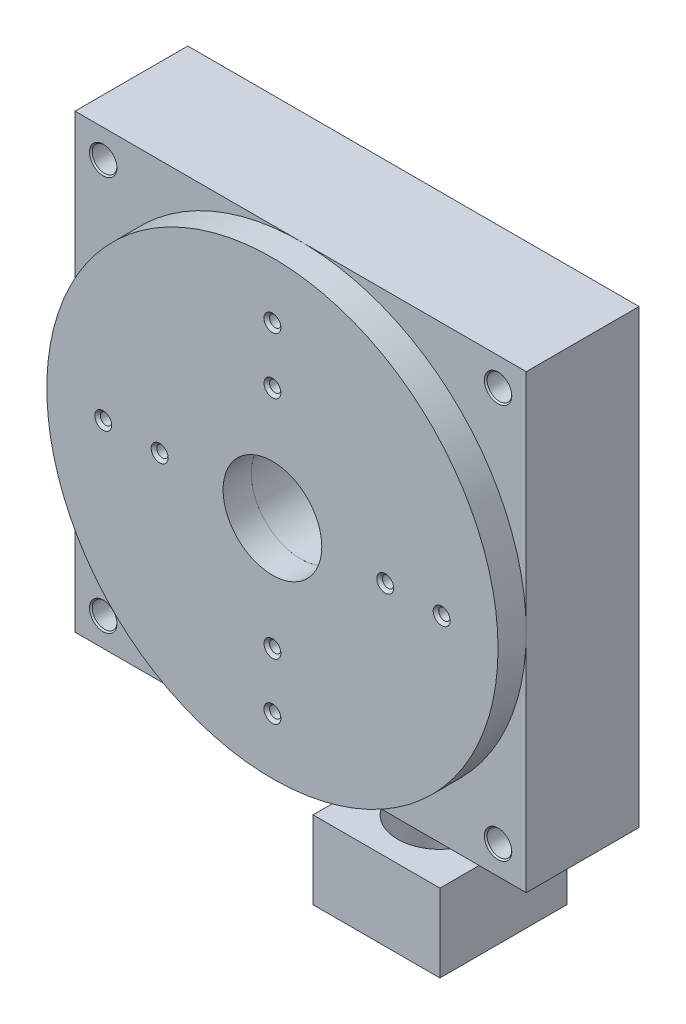
SolidWorks part; units mm, degrees
material "6061-T6 (SS)"
ref_plane "Front Plane" through (0, 0, 0) normal (0, 0, 1) x (1, 0, 0)
ref_plane "Top Plane" through (0, 0, 0) normal (0, 1, 0) x (1, 0, 0)
ref_plane "Right Plane" through (0, 0, 0) normal (1, 0, 0) x (0, 0, -1)
sketch "Sketch1" plane through (0, 0, 0) normal (0, 0, 1) x (1, 0, 0)
  circle A0 centre (0, 0) radius 101.6
  circle A1 centre (0, 0) radius 22.225
  dimension "D1" = 203.2
  dimension "D2" = 44.45
extrude "Boss-Extrude1" add sketch "Sketch1" along normal blind 12.7
hole_wizard "1/4-20 Tapped Hole1" positions "Sketch2" profile "Sketch3" tap size "1/4-20" standard "ANSI Inch" end condition up to next
sketch "Sketch2" plane through (0, 0, 12.7) normal (0, 0, 1) x (1, 0, 0)
  line L0 (0, 0) -> (0, 76.2) construction
  point P2 (0, 76.2)
  point P8 (0, 50.8)
  point P13 (76.2, 0)
  point P14 (50.8, 0)
  point P15 (0, -76.2)
  point P16 (0, -50.8)
  point P17 (-76.2, 0)
  point P18 (-50.8, 0)
  dimension "D1" = 50.8
  dimension "D2" = 76.2
  dimension "D3" = 4
cosmetic thread "Hole Thread1"
cosmetic thread "Hole Thread2"
cosmetic thread "Hole Thread3"
cosmetic thread "Hole Thread4"
cosmetic thread "Hole Thread5"
cosmetic thread "Hole Thread6"
cosmetic thread "Hole Thread7"
cosmetic thread "Hole Thread8"
sketch "Sketch3" plane through (-50.8, 0, 12.7) normal (1, 0, 0) x (0, -1, 0)
  line L0 (0, 0) -> (0, 12.7)
  line L1 (0, 12.7) -> (3.81, 12.7)
  line L2 (2.5527, 11.4427) -> (2.5527, 1.2573)
  line L3 (2.5527, 1.2573) -> (3.81, 0)
  line L5 (3.81, 0) -> (0, 0)
  line L6 (-2.5527, 1.2573) -> (-3.81, 0) construction
  line L7 (3.81, 12.7) -> (2.5527, 11.4427)
  line L8 (-3.81, 12.7) -> (-2.5527, 11.4427) construction
  line L11 (0, -6.35) -> (0, 107.95) construction
  dimension "Thru Tap Drill Dia." = 5.1054
  dimension "Thru Tap Drill Depth" = 12.7
  dimension "Near C'Sink Dia." = 7.62
  dimension "Near C'Sink Angle" = 90
  dimension "Far C'Sink Dia." = 7.62
  dimension "Far C'Sink Angle" = 90
sketch "Sketch4" plane through (0, 0, 0) normal (0, 0, -1) x (-1, 0, 0)
  line L1 (101.6, 101.6) -> (-101.6, 101.6)
  line L2 (101.6, 101.6) -> (101.6, -101.6)
  line L3 (101.6, -101.6) -> (-101.6, -101.6)
  line L4 (-101.6, 101.6) -> (-101.6, -101.6)
  line L5 (0, -101.6) -> (0, 101.6) construction
  line L6 (101.6, 0) -> (-101.6, 0) construction
  circle A1 centre (0, 0) radius 22.225
  circle A2 centre (0, 0) radius 22.225 construction
  point P0 (0, 0)
  dimension "D1" = 203.2
extrude "Boss-Extrude2" add sketch "Sketch4" along normal blind 50.8 separate body
hole_wizard "CBORE for 1/4 Socket Head Cap Screw1" positions "Sketch5" profile "Sketch6" counterbore size "1/4" standard "ANSI Inch" end condition up to next
sketch "Sketch5" plane through (0, 0, 0) normal (0, 0, 1) x (1, 0, 0)
  line L1 (88.9, 88.9) -> (-88.9, 88.9) construction
  line L2 (88.9, 88.9) -> (88.9, -88.9) construction
  line L3 (88.9, -88.9) -> (-88.9, -88.9) construction
  line L4 (-88.9, 88.9) -> (-88.9, -88.9) construction
  line L5 (88.9, 88.9) -> (-88.9, -88.9) construction
  line L6 (88.9, -88.9) -> (-88.9, 88.9) construction
  point P2 (-88.9, -88.9)
  point P53 (88.9, 88.9)
  point P54 (88.9, -88.9)
  point P55 (-88.9, 88.9)
  point P61 (0, 0)
  dimension "D1" = 177.8
sketch "Sketch6" plane through (-88.9, -88.9, 0) normal (1, 0, 0) x (0, -1, 0)
  line L0 (0, 0) -> (0, 50.8)
  line L1 (3.2639, 50.165) -> (3.8989, 50.8)
  line L2 (5.5562, 44.45) -> (3.2639, 44.45)
  line L3 (3.2639, 44.45) -> (3.2639, 50.165)
  line L5 (5.5562, 44.45) -> (5.5562, 0.635)
  line L6 (5.5562, 0.635) -> (6.1913, 0)
  line L7 (6.1913, 0) -> (0, 0)
  line L8 (-5.5562, 0.635) -> (-6.1913, 0) construction
  line L11 (0, -6.35) -> (0, 107.95) construction
  line L12 (3.8989, 50.8) -> (0, 50.8)
  line L13 (-3.2639, 50.165) -> (-3.8989, 50.8) construction
  dimension "Thru Hole Dia." = 6.5278
  dimension "Thru Hole Depth" = 50.8
  dimension "C'Bore Dia." = 11.1125
  dimension "C'Bore Depth" = 44.45
  dimension "Near C'Sink Dia." = 12.3825
  dimension "Near C'Sink Angle" = 90
  dimension "Far C'Sink Dia." = 7.7978
  dimension "Far C'Sink Angle" = 90
sketch "Sketch7" plane through (0, -101.6, 0) normal (0, -1, 0) x (1, 0, 0)
  line L0 (101.6, -50.8) -> (-101.6, -50.8) construction
  line L1 (80.391, 17.653) -> (23.241, 17.653)
  line L2 (80.391, 17.653) -> (80.391, -39.497)
  line L3 (80.391, -39.497) -> (23.241, -39.497)
  line L4 (23.241, 17.653) -> (23.241, -39.497)
  line L5 (80.391, 17.653) -> (23.241, -39.497) construction
  line L6 (80.391, -39.497) -> (23.241, 17.653) construction
  circle A0 centre (51.816, -10.922) radius 19.05
  point P0 (51.816, -10.922)
  dimension "D4" = 38.1
  dimension "D1" = 57.15
  dimension "D2" = 51.816
  dimension "D3" = 39.878
extrude "Boss-Extrude3" add sketch "Sketch7" along normal blind 35.052
hole_wizard "#10-24 Tapped Hole1" positions "Sketch8" profile "Sketch10" tap size "#10-24" standard "ANSI Inch"
sketch "Sketch8" plane through (0, -136.652, 0) normal (0, -1, 0) x (-1, 0, 0)
  line L1 (-75.438, 34.544) -> (-28.194, 34.544) construction
  line L2 (-75.438, 34.544) -> (-75.438, -12.7) construction
  line L3 (-75.438, -12.7) -> (-28.194, -12.7) construction
  line L4 (-28.194, 34.544) -> (-28.194, -12.7) construction
  line L7 (-51.816, 29.972) -> (-51.816, -8.128) construction
  line L9 (-28.194, 34.544) -> (-75.438, -12.7) construction
  arc A3 (-36.2079, 0) -> (-67.4241, 0) centre (-51.816, 10.922) ccw construction
  circle A4 centre (-51.816, 10.922) radius 19.05 construction
  point P1 (-28.194, -12.7)
  point P170 (-75.438, 34.544)
  point P171 (-75.438, -12.7)
  point P172 (-28.194, 34.544)
  point P205 (-51.816, 10.922)
  dimension "D1" = 47.244
sketch "Sketch10" plane through (28.194, -136.652, 12.7) normal (1, 0, 0) x (0, 0, -1)
  line L0 (0, 0) -> (0, 26.5408)
  line L1 (0, 26.5408) -> (1.8986, 25.4)
  line L2 (1.8986, 25.4) -> (1.8986, 1.1494)
  line L3 (1.8986, 1.1494) -> (3.048, 0)
  line L5 (3.048, 0) -> (0, 0)
  line L6 (-1.8986, 1.1494) -> (-3.048, 0) construction
  line L10 (0, 26.5408) -> (-1.8987, 25.4) construction
  line L11 (0, -6.35) -> (0, 107.95) construction
  dimension "Tap Drill Dia." = 3.7973
  dimension "Tap Drill Depth" = 25.4
  dimension "Near C'Sink Dia." = 6.096
  dimension "Near C'Sink Angle" = 90
  dimension "Drill Angle" = 118
cosmetic thread "Hole Thread9"
cosmetic thread "Hole Thread10"
cosmetic thread "Hole Thread11"
cosmetic thread "Hole Thread12"
ref_axis "Axis1" through (0, 0, 12.7) along (0, 0, -1)
